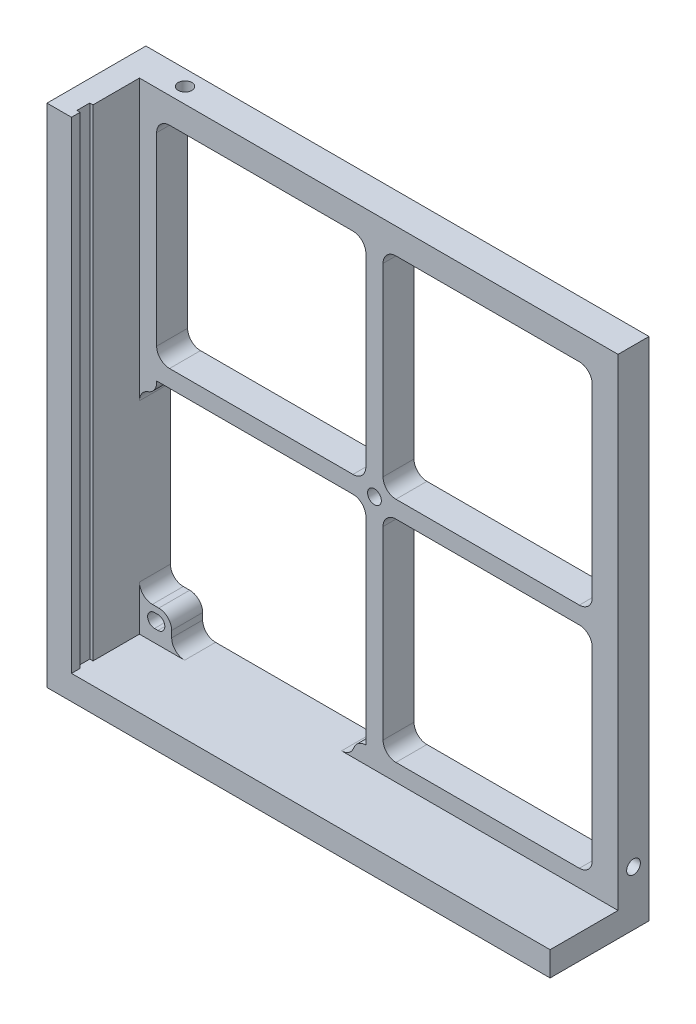
SolidWorks part; units mm, degrees
note: The reader was unsure of these and kept them because the rebuilt part matched: shared geometry of "Sketch3<3>", "Sketch5<3>", "Sketch7<5>", "Sketch9<3>".
ref_plane "Front Plane" through (0, 0, 0) normal (0, 0, 1) x (1, 0, 0)
ref_plane "Top Plane" through (0, 0, 0) normal (0, 1, 0) x (1, 0, 0)
ref_plane "Right Plane" through (0, 0, 0) normal (1, 0, 0) x (0, 0, -1)
sketch "Sketch1" plane through (0, 0, 0) normal (0, 0, 1) x (1, 0, 0)
  line L0 (117, 0) -> (117, 235.4) construction
  line L1 (0, 0) -> (234, 0)
  line L2 (0, 0) -> (0, 235.4)
  line L3 (0, 235.4) -> (234, 235.4)
  line L4 (234, 0) -> (234, 235.4)
  line L5 (0, 117.7) -> (234, 117.7) construction
  line L6 (117, 0) -> (117, 5.7)
  line L7 (117, 5.7) -> (5.7, 5.7)
  line L8 (5.7, 5.7) -> (5.7, 117.7)
  line L9 (5.7, 117.7) -> (0, 117.7)
  dimension "D1" = 234
  dimension "D2" = 235.4
  dimension "D3" = 5.7
  dimension "D4" = 5.7
extrude "Boss-Extrude1" add sketch "Sketch1" along normal blind 23 contours L8 L9 L2 L1 L6 L7
sketch "Sketch2" plane through (5.7, 0, 0) normal (1, 0, 0) x (0, 0, -1)
  line L0 (-23, 5.7) -> (0, 5.7) construction
  line L1 (-21, 5.7) -> (-18, 5.7)
  line L2 (-21, 5.7) -> (-21, 117.7)
  line L3 (-21, 117.7) -> (-18, 117.7)
  line L4 (-18, 5.7) -> (-18, 117.7)
  line L5 (-23, 117.7) -> (0, 117.7) construction
  line L6 (-23, 5.7) -> (-23, 117.7) construction
  dimension "D1" = 2
  dimension "D2" = 3
extrude "Cut-Extrude1" cut sketch "Sketch2" against normal blind 0.75 contours L2 L1 L4 L3
sketch "Sketch3" plane through (5.7, 0, 0) normal (1, 0, 0) x (0, 0, -1)
  line L0 (-18, 117.7) -> (0, 117.7) construction
  line L1 (0, 5.7) -> (0, 117.7) construction
  line L2 (-7.2, 117.7) -> (0, 117.7)
  line L3 (-7.2, 117.7) -> (-7.2, 111.7)
  line L4 (-7.2, 111.7) -> (0, 111.7)
  line L5 (0, 117.7) -> (0, 111.7)
  line L6 (-23, 5.7) -> (-23, 117.7) construction
  line L8 (-7.2, 111.7) -> (0, 111.7)
  line L9 (-7.2, 111.7) -> (-7.2, 5.7)
  line L10 (-7.2, 5.7) -> (0, 5.7)
  line L11 (0, 111.7) -> (0, 5.7)
  line M8 (0, 117.7) -> (-18, 117.7)
  line M10 (-18, 5.7) -> (0, 5.7)
  line M11 (0, 5.7) -> (0, 117.7)
  dimension "D1" = 15.8
  dimension "D2" = 6
extrude "Boss-Extrude2" add sketch "Sketch3" along normal blind 10 contours L3 L4 M11 M8
extrude "Boss-Extrude3" add sketch "Sketch3<3>" along normal blind 4 contours L4 L9 M10 M11
sketch "Sketch3<3>" plane through (5.7, 0, 0) normal (1, 0, 0) x (0, 0, -1) same geometry as "Sketch3"
fillet "Fillet1" radius 3 1 edges at (9.7, 111.7, 3.6)
sketch "Sketch5" plane through (0, 5.7, 0) normal (0, 1, 0) x (1, 0, 0)
  line L0 (117, -23) -> (5.7, -23) construction
  line L1 (117, 0) -> (111, 0)
  line L2 (117, 0) -> (117, -7.2)
  line L3 (117, -7.2) -> (111, -7.2)
  line L4 (111, 0) -> (111, -7.2)
  line L5 (9.7, -7.2) -> (111, -7.2)
  line L6 (9.7, -7.2) -> (9.7, 0)
  line L7 (9.7, 0) -> (111, 0)
  line L8 (111, -7.2) -> (111, 0)
  line M16 (117, -23) -> (117, 0)
  line M17 (117, 0) -> (9.7, 0)
  line M18 (9.7, 0) -> (9.7, -7.2)
  dimension "D1" = 15.8
  dimension "D2" = 6
extrude "Boss-Extrude4" add sketch "Sketch5" along normal blind 4 contours L5 L8 L4 M17 M18
extrude "Boss-Extrude5" add sketch "Sketch5<3>" along normal blind 10 contours L4 L3 M17 M16
sketch "Sketch5<3>" plane through (0, 5.7, 0) normal (0, 1, 0) x (1, 0, 0) same geometry as "Sketch5"
fillet "Fillet3" radius 3 1 edges at (111, 9.7, 3.6)
sketch "Sketch6" plane through (0, 0, 7.2) normal (0, 0, 1) x (1, 0, 0)
  line L1 (5.7, 5.7) -> (55.7, 5.7)
  line L2 (5.7, 5.7) -> (5.7, 55.7)
  line L3 (5.7, 55.7) -> (55.7, 55.7)
  line L4 (55.7, 5.7) -> (55.7, 55.7)
  dimension "D1" = 50
  dimension "D2" = 50
extrude "Cut-Extrude2" cut sketch "Sketch6" against normal through all
fillet "Fillet8" radius 3 1 edges at (5.7, 55.7, 3.6)
fillet "Fillet9" radius 3 1 edges at (9.7, 55.7, 3.6)
fillet "Fillet10" radius 3 1 edges at (55.7, 5.7, 3.6)
fillet "Fillet11" radius 3 1 edges at (55.7, 9.7, 3.6)
sketch "Sketch7" plane through (117, 0, 0) normal (1, 0, 0) x (0, 0, -1)
  line L0 (0, 0) -> (0, 15.7) construction
  line L1 (-7.2, 15.7) -> (0, 15.7) construction
  circle A0 centre (-3.6, 12.7) radius 1.6
  circle A1 centre (-3.6, 12.7) radius 1
  dimension "D1" = 3.2
  dimension "D4" = 2
  dimension "D2" = 3.6
  dimension "D3" = 3
extrude "Cut-Extrude3" cut sketch "Sketch7" against normal up to next and the other way through all contours A1
extrude "Cut-Extrude4" cut sketch "Sketch7<5>" against normal blind 3.2
sketch "Sketch7<5>" plane through (117, 0, 0) normal (1, 0, 0) x (0, 0, -1) same geometry as "Sketch7"
sketch "Sketch8" plane through (117, 0, 0) normal (1, 0, 0) x (0, 0, -1)
  circle A0 centre (-3.6, 12.7) radius 2
  dimension "D1" = 4
extrude "Cut-Extrude6" cut sketch "Sketch8" against normal blind 3 from offset 5.5 offset against normal yes
sketch "Sketch9" plane through (0, 117.7, 0) normal (0, 1, 0) x (1, 0, 0)
  line L0 (15.7, 0) -> (15.7, -7.2) construction
  line L1 (15.7, 0) -> (0, 0) construction
  circle A0 centre (12.7, -3.6) radius 1.6
  circle A1 centre (12.7, -3.6) radius 1
  dimension "D1" = 3
  dimension "D2" = 3.2
  dimension "D4" = 2
  dimension "D3" = 3.6
extrude "Cut-Extrude7" cut sketch "Sketch9" against normal up to next contours A1
extrude "Cut-Extrude8" cut sketch "Sketch9<3>" against normal blind 3.2
sketch "Sketch9<3>" plane through (0, 117.7, 0) normal (0, 1, 0) x (1, 0, 0) same geometry as "Sketch9"
sketch "Sketch10" plane through (0, 117.7, 0) normal (0, 1, 0) x (1, 0, 0)
  circle A0 centre (12.7, -3.6) radius 2
  dimension "D1" = 4
extrude "Cut-Extrude9" cut sketch "Sketch10" against normal blind 3.2 from offset 5.5 offset against normal yes
sketch "Sketch11" plane through (0, 0, 0) normal (0, 0, -1) x (-1, 0, 0)
  line L1 (-117, 15.7) -> (-111, 15.7)
  line L2 (-117, 15.7) -> (-117, 117.7)
  line L3 (-117, 117.7) -> (-63.35, 117.7)
  line L4 (-111, 15.7) -> (-111, 111.7)
  line L5 (-15.7, 117.7) -> (-63.35, 117.7)
  line L6 (-15.7, 117.7) -> (-15.7, 111.7)
  line L7 (-15.7, 111.7) -> (-111, 111.7)
  point P8 (0, 0)
  point P9 (0, 0)
  point P10 (0, 0)
  point P12 (-115.658, 117.7)
  point P13 (0, 0)
  point P14 (-63.35, 117.7)
  dimension "D1" = 6
  dimension "D2" = 6
extrude "Boss-Extrude6" add sketch "Sketch11" against normal blind 7.2
fillet "Fillet12" radius 3 1 edges at (111, 111.7, 3.6)
sketch "Sketch12" plane through (0, 0, 0) normal (0, 0, -1) x (-1, 0, 0)
  line L0 (-111, 60.7) -> (-9.7, 60.7) construction
  line L1 (-111, 12.7) -> (-9.7, 12.7) construction
  line L2 (-111, 12.7) -> (-111, 108.7) construction
  line L3 (-111, 108.7) -> (-9.7, 108.7) construction
  line L4 (-9.7, 12.7) -> (-9.7, 108.7) construction
  line L5 (-60.35, 108.7) -> (-60.35, 12.7) construction
  line L6 (-62.35, 12.7) -> (-62.35, 9.7)
  line L7 (-111, 58.7) -> (-62.35, 58.7)
  line L8 (-111, 58.7) -> (-111, 62.7)
  line L9 (-111, 62.7) -> (-62.35, 62.7)
  line L10 (-9.7, 58.7) -> (-9.7, 62.7)
  line L11 (-58.35, 108.7) -> (-62.35, 108.7) construction
  line L12 (-58.35, 108.7) -> (-58.35, 62.7)
  line L13 (-58.35, 12.7) -> (-62.35, 12.7) construction
  line L14 (-62.35, 108.7) -> (-62.35, 62.7)
  line L15 (-108, 9.7) -> (-58.3569, 9.7) construction
  line L16 (-62.35, 9.7) -> (-58.3569, 9.7)
  line L17 (-58.3569, 9.7) -> (-58.35, 12.7)
  line L18 (-62.35, 108.7) -> (-62.35, 111.7)
  line L19 (-108, 111.7) -> (-12.7, 111.7) construction
  line L20 (-62.35, 111.7) -> (-58.35, 111.7)
  line L21 (-58.35, 111.7) -> (-58.35, 108.7)
  line L22 (-62.35, 58.7) -> (-62.35, 12.7)
  line L23 (-58.35, 58.7) -> (-9.7, 58.7)
  line L24 (-58.35, 62.7) -> (-9.7, 62.7)
  line L25 (-58.35, 58.7) -> (-58.35, 12.7)
  dimension "D1" = 2
  dimension "D2" = 2
  dimension "D3" = 2
  dimension "D4" = 2
extrude "Boss-Extrude7" add sketch "Sketch12" against normal blind 7.2
fillet "Fillet13" radius 3 3 edges at (111, 62.7, 3.6) (62.35, 62.7, 3.6) (62.35, 111.7, 3.6)
fillet "Fillet14" radius 3 3 edges at (62.35, 58.7, 3.6) (62.35, 9.7, 3.6) (111, 58.7, 3.6)
fillet "Fillet15" radius 3 3 edges at (9.7, 62.7, 3.6) (58.35, 111.7, 3.6) (58.35, 62.7, 3.6)
fillet "Fillet16" radius 3 1 edges at (58.35, 58.7, 3.6)
sketch "Sketch13" plane through (0, 0, 0) normal (0, 0, -1) x (-1, 0, 0)
  line L0 (-5.7, 20.7) -> (-20.7, 5.7)
  line L1 (-5.7, 5.7) -> (-20.7, 5.7)
  line L2 (-5.7, 5.7) -> (-5.7, 20.7)
  line L3 (-5.7, 20.7) -> (-20.7, 20.7) construction
  line L4 (-20.7, 5.7) -> (-20.7, 20.7) construction
  dimension "D1" = 15
  dimension "D2" = 15
extrude "Boss-Extrude8" add sketch "Sketch13" against normal blind 7.2
sketch "Sketch14" plane through (0, 0, 7.2) normal (0, 0, 1) x (1, 0, 0)
  line L0 (20.7, 5.7) -> (5.7, 5.7) construction
  line L1 (5.7, 5.7) -> (5.7, 20.7) construction
  line L2 (10, 8.6) -> (9.2, 8.6)
  line L3 (10, 11.8) -> (9.2, 11.8)
  arc A0 (10, 8.6) -> (10, 11.8) centre (10, 10.2) ccw
  arc A1 (9.2, 11.8) -> (9.2, 8.6) centre (9.2, 10.2) ccw
  dimension "D1" = 4.5
  dimension "D3" = 3.2
  dimension "D4" = 3.2
  dimension "D2" = 4.3
  dimension "D5" = 4.5
  dimension "D6" = 3.5
extrude "Cut-Extrude10" cut sketch "Sketch14" against normal up to next
sketch "Sketch15" plane through (0, 0, 7.2) normal (0, 0, 1) x (1, 0, 0)
  line L1 (20.7, 5.7) -> (13.2, 5.7)
  line L2 (20.7, 5.7) -> (20.7, 20.7)
  line L3 (20.7, 20.7) -> (13.2, 20.7)
  line L4 (13.2, 5.7) -> (13.2, 13.2)
  line L5 (5.7, 20.7) -> (20.7, 20.7)
  line L6 (5.7, 20.7) -> (5.7, 13.2)
  line L7 (5.7, 13.2) -> (13.2, 13.2)
  line L8 (20.7, 20.7) -> (20.7, 13.2)
  point P8 (0, 0)
  point P9 (0, 0)
  point P10 (0, 0)
  line M13 (5.7, 20.7) -> (5.7, 5.7)
  line M14 (5.7, 5.7) -> (20.7, 5.7)
  line M15 (20.7, 5.7) -> (5.7, 20.7)
  dimension "D1" = 7.5
  dimension "D2" = 7.5
extrude "Cut-Extrude11" cut sketch "Sketch15" against normal up to next (7.2 mm away) contours L4 M14 M15 | L7 M13 M15 | L5 L2 L3 M15
fillet "Fillet17" radius 3 3 edges at (5.7, 13.2, 3.6) (13.2, 13.2, 3.6) (13.2, 5.7, 3.6)
sketch "Sketch16" plane through (0, 0, 0) normal (0, 0, -1) x (-1, 0, 0)
  line L0 (-65.35, 62.7) -> (-108, 62.7) construction
  line L2 (-58.35, 12.7) -> (-58.35, 55.7) construction
  circle A0 centre (-60.35, 60.7) radius 1.6
  dimension "D1" = 2
  dimension "D3" = 3.2
  dimension "D2" = 2
extrude "Cut-Extrude12" cut sketch "Sketch16" against normal up to next
